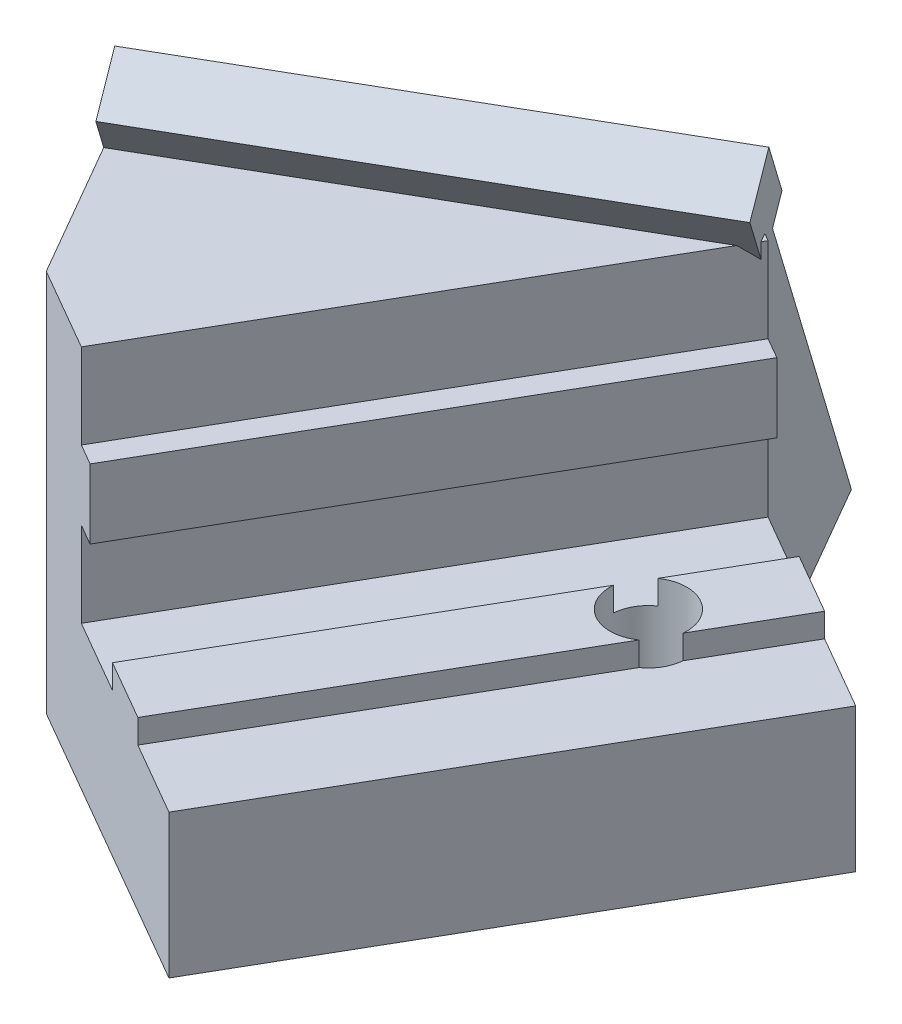
SolidWorks part; units mm, degrees
ref_plane "Front Plane" through (0, 0, 0) normal (0, 0, 1) x (1, 0, 0)
ref_plane "Top Plane" through (0, 0, 0) normal (0, 1, 0) x (1, 0, 0)
ref_plane "Right Plane" through (0, 0, 0) normal (1, 0, 0) x (0, 0, -1)
sketch "Esquisse1" plane through (0, 0, 0) normal (0, 0, 1) x (1, 0, 0)
  line L0 (8, 16) -> (17.2376, 0)
  line L1 (17.2376, 0) -> (0, 0)
  line L2 (0, 0) -> (0, 16)
  line L3 (0, 16) -> (8, 16)
  dimension "D1" = 8
  dimension "D2" = 120
  dimension "D3" = 16
extrude "Boss.-Extru.1" add sketch "Esquisse1" along normal blind 20
sketch "Esquisse2" plane through (12.9282, 7.4641, 0) normal (0.866, 0.5, 0) x (0, 0, -1)
  line L0 (-20, -8.6188) -> (0, -8.6188) construction
  line L3 (-20, -8.6188) -> (-20, 9.8564) construction
  circle A0 centre (-10, -0.6188) radius 1.6
  dimension "D1" = 3.2
  dimension "D2" = 8
  dimension "D3" = 10
extrude "HoleForLauncherFixing" cut sketch "Esquisse2" against normal through all
ref_plane "Plan1" through (8.5981, 4.9641, 0) normal (0.866, 0.5, 0) x (0, 0, -1)
ref_axis "Axe1" through (3.208, 14.3, 0) along (0.5, -0.866, 0)
ref_plane "Plan3" through (0, 0, 0) normal (-0.866, 0, -0.5) x (0, -1, 0)
sketch "Esquisse4" plane through (0, 0, 0) normal (-0.866, 0, -0.5) x (0, -1, 0)
  line L1 (4.4994, 17.8157) -> (-17.7877, 17.8157)
  line L2 (4.4994, 17.8157) -> (4.4994, -17.0003)
  line L3 (4.4994, -17.0003) -> (-17.7877, -17.0003)
  line L4 (-17.7877, 17.8157) -> (-17.7877, -17.0003)
extrude "Enlèv. mat.-Extru.3" cut sketch "Esquisse4" against normal blind 6
ref_plane "Plan4" through (1.7321, 0, -3) normal (-0.5, 0, 0.866) x (0, 1, 0)
ref_plane "Plan5" through (0, 0, 12) normal (0.5, 0, -0.866) x (-0.866, 0, -0.5)
ref_plane "Plan6" through (-8.6603, 0, 15) normal (0.5, 0, -0.866) x (-0.866, 0, -0.5)
sketch "Esquisse5" plane through (-3.4641, 0, 18) normal (0.5, 0, -0.866) x (-0.866, 0, -0.5)
  line L0 (-4, 0) -> (10, 0)
  line L1 (10, 0) -> (10, 6)
  line L2 (10, 6) -> (6.45, 6)
  line L3 (6.45, 6) -> (6.45, 7)
  line L4 (6.45, 7) -> (3.55, 7)
  line L5 (3.55, 7) -> (3.55, 6)
  line L6 (3.55, 6) -> (0, 6)
  line L7 (0, 6) -> (0, 9.55)
  line L8 (0, 9.55) -> (1, 9.55)
  line L9 (1, 9.55) -> (1, 12.45)
  line L10 (1, 12.45) -> (0, 12.45)
  line L11 (0, 12.45) -> (0, 16)
  line L12 (0, 16) -> (-4, 16)
  line L13 (-4, 16) -> (-4, 0)
  dimension "D1" = 10
  dimension "D2" = 2.9
  dimension "D3" = 1
  dimension "D4" = 6
  dimension "D5" = 4
  dimension "D6" = 10
extrude "MakerBeanFixing" add sketch "Esquisse5" along normal blind 21
sketch "Esquisse6" plane through (12.9282, 7.4641, 0) normal (0.866, 0.5, 0) x (0, 0, -1)
  line L0 (0, -8.6188) -> (0, 9.8564) construction
  line L1 (0, 9.3812) -> (-20, 9.3812)
  line L2 (0, 9.3812) -> (0, 12.3812)
  line L3 (0, 12.3812) -> (-20, 12.3812)
  line L4 (-20, 9.3812) -> (-20, 12.3812)
  line L5 (-20, -8.6188) -> (0, -8.6188) construction
  dimension "D1" = 18
  dimension "D2" = 3
extrude "AntiRotationSystem" add sketch "Esquisse6" along normal mid plane 2.5
sketch "Esquisse7" plane through (0, 7, 0) normal (0, 1, 0) x (1, 0, 0)
  line L2 (1.45, 3.4115) -> (3.9615, 1.9615) construction
  line L3 (3.9615, 1.9615) -> (-6.5385, -16.225) construction
  circle A0 centre (0.2058, -1.6436) radius 1.6
  dimension "D1" = 3.2
  dimension "D2" = 5
  dimension "D3" = 1.45
extrude "TopMakerBeanFixingHole" cut sketch "Esquisse7" against normal through all
sketch "Esquisse8" plane through (0, 0, 0) normal (0, 0, -1) x (-1, 0, 0)
  line L0 (-8.2376, 15.5885) -> (-17.2376, 0)
  line L1 (-17.2376, 0) -> (-8.2376, 15.5885) construction
  line L2 (-17.2376, 0) -> (-20.9182, 2.125)
  line L3 (-20.9182, 2.125) -> (-10.4182, 20.3115)
  line L4 (-8.2376, 15.5885) -> (-9.3201, 16.2135)
  line L6 (-17.2376, 0) -> (-8.2376, 15.5885) construction
  line L9 (-9.3201, 16.2135) -> (-7.8201, 18.8115)
  line L10 (-7.8201, 18.8115) -> (-10.4182, 20.3115)
  dimension "D1" = 3
extrude "Enlèv. mat.-Extru.4" cut sketch "Esquisse8" against normal through all
sketch "Esquisse3" plane through (8.5981, 4.9641, 0) normal (0.866, 0.5, 0) x (0, 0, -1)
  circle A0 centre (-10, -0.6188) radius 4.25
  circle A1 centre (-10, -0.6188) radius 1.6 construction
  dimension "D1" = 8.5
extrude "BigHoleForLauncherFixing" cut sketch "Esquisse3" against normal through all
mirror "Symétrie1" about plane through (-1.6244, 0, -5.1865) normal (0.866, 0, 0.5) of bodies 103
sketch "Esquisse9" plane through (1.8397, 0, -3.1865) normal (0.5, 0, -0.866) x (-0.866, 0, -0.5)
  line L0 (-6.3731, 0) -> (4, 0) construction
  line L1 (4, 0) -> (-24.9282, 0)
  line L2 (4, 0) -> (4, 18.8115)
  line L3 (4, 18.8115) -> (-24.9282, 18.8115)
  line L4 (-24.9282, 0) -> (-24.9282, 18.8115)
  line L5 (4, 0) -> (4, 6) construction
extrude "Enlèv. mat.-Extru.5" cut sketch "Esquisse9" against normal through all both and the other way through all
